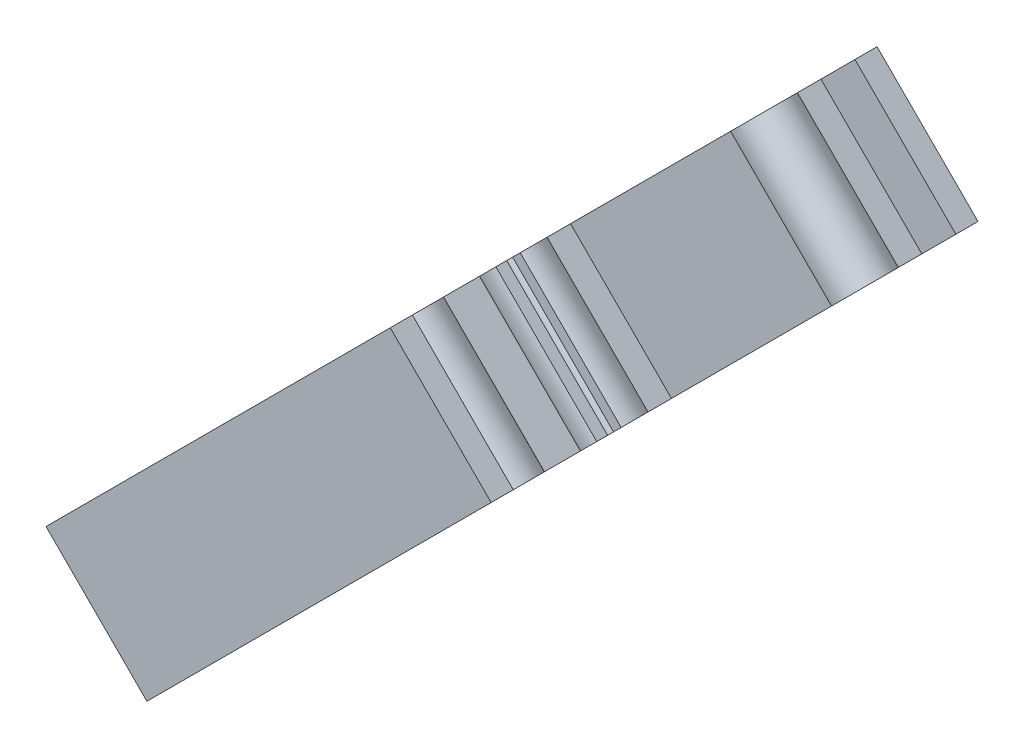
SolidWorks part; units mm, degrees
ref_plane "Front Plane" through (0, 0, 0) normal (0, 0, 1) x (1, 0, 0)
ref_plane "Top Plane" through (0, 0, 0) normal (0, 1, 0) x (1, 0, 0)
ref_plane "Right Plane" through (0, 0, 0) normal (1, 0, 0) x (0, 0, -1)
sketch "Sketch2" plane through (-7.3783, 7.3783, 0) normal (-0.7071, 0.7071, 0) x (0, 0, 1)
  line L0 (56.3, -19.0919) -> (56.3, -16.7419)
  line L1 (21.3, -14.0919) -> (51.3, -14.0919)
  line L2 (21.3, -14.0919) -> (21.3, 15.9081)
  line L3 (21.3, 15.9081) -> (51.3, 15.9081)
  line L4 (51.3, -14.0919) -> (51.3, 15.9081)
  line L5 (21.3, -14.0919) -> (51.3, 15.9081) construction
  line L6 (21.3, 15.9081) -> (51.3, -14.0919) construction
  line L7 (14.3, -21.0919) -> (58.3, -21.0919)
  line L8 (14.3, -21.0919) -> (14.3, 22.9081)
  line L10 (58.3, -21.0919) -> (58.3, 22.9081)
  line L11 (14.3, -21.0919) -> (58.3, 22.9081) construction
  line L12 (14.3, 22.9081) -> (58.3, -21.0919) construction
  line L13 (16.3, -19.0919) -> (56.3, -19.0919)
  line L14 (16.3, -19.0919) -> (16.3, -16.7419)
  line L15 (14.3, 22.9081) -> (16.3, 22.9081)
  line L16 (56.3, 22.9081) -> (58.3, 22.9081)
  line L17 (54.1782, 18.5581) -> (56.3, 18.5581)
  line L18 (18.4218, 18.5581) -> (16.3, 18.5581)
  line L20 (18.4218, 15.2581) -> (16.3, 15.2581)
  line L24 (54.1782, 15.2581) -> (56.3, 15.2581)
  line L26 (18.4218, -13.4419) -> (16.3, -13.4419)
  line L28 (18.4218, -16.7419) -> (16.3, -16.7419)
  line L30 (54.1782, -16.7419) -> (56.3, -16.7419)
  line L32 (54.1782, -13.4419) -> (56.3, -13.4419)
  line L34 (56.3, 18.5581) -> (56.3, 22.9081)
  line L35 (14.3, -21.0919) -> (58.3, -21.0919) construction
  line L36 (56.3, -19.0919) -> (56.3, 22.9081) construction
  line L37 (56.3, -13.4419) -> (56.3, 15.2581)
  line L38 (16.3, -13.4419) -> (16.3, 15.2581)
  line L39 (16.3, -19.0919) -> (16.3, 22.9081) construction
  line L40 (16.3, 18.5581) -> (16.3, 22.9081)
  circle A0 centre (20.3, 16.9081) radius 1.65
  circle A1 centre (52.3, 16.9081) radius 1.65
  circle A2 centre (20.3, -15.0919) radius 1.65
  circle A3 centre (52.3, -15.0919) radius 1.65
  arc A4 (18.4218, 15.2581) -> (18.4218, 18.5581) centre (20.3, 16.9081) ccw
  arc A5 (54.1782, 18.5581) -> (54.1782, 15.2581) centre (52.3, 16.9081) ccw
  arc A6 (18.4218, -16.7419) -> (18.4218, -13.4419) centre (20.3, -15.0919) ccw
  arc A7 (54.1782, -13.4419) -> (54.1782, -16.7419) centre (52.3, -15.0919) ccw
  point P0 (36.3, 0.9081)
  point P5 (36.3, 0.9081)
  point P30 (0, 0)
  point P44 (60.3367, 21.5129)
  line M7 (58.3, 22.9081) -> (14.3, 22.9081)
  line M8 (14.3, 22.9081) -> (14.3, -21.0919)
  line M9 (14.3, -21.0919) -> (58.3, -21.0919)
  line M10 (58.3, -21.0919) -> (58.3, 22.9081)
  line M11 (21.3, -13.0919) -> (21.3, 14.9081)
  line M13 (22.3, 15.9081) -> (50.3, 15.9081)
  line M15 (51.3, 14.9081) -> (51.3, -13.0919)
  line M17 (50.3, -14.0919) -> (22.3, -14.0919)
  dimension "D2" = 3.3
  dimension "D5" = 3.3
  dimension "D6" = 3.3
  dimension "D7" = 3.3
  dimension "D8" = 5
  dimension "D9" = 5
  dimension "D10" = 5
  dimension "D11" = 5
  dimension "D1" = 2
  dimension "D3" = 30
  dimension "D4" = 30
  dimension "D12" = 2.1218
  dimension "D13" = 3.3
extrude "Boss-Extrude1" add sketch "Sketch2" along normal blind 12.9 contours L32 A7 L4 A3 L1 L30 L0 L13 L14 L28 A6 A2 L2 L26 L38 L20 A4 A0 L3 L18 L40 L34 L17 A5 A1 L24 L37 M15 M17 M11 M13 M7 M8 M9 M10 region at (-20.0475, -5.2908, 56.9223)
fillet "Fillet1" radius 5 2 edges at (-25.4392, -1.5608, 56.3) (-25.4392, -1.5608, 16.3)
fillet "Fillet2" radius 1 2 edges at (-23.7775, 0.1009, 16.3) (-23.7775, 0.1009, 56.3)
fillet "Fillet3" radius 0.5 2 edges at (-23.7775, 0.1009, 54.1782) (-23.7775, 0.1009, 18.4218)
